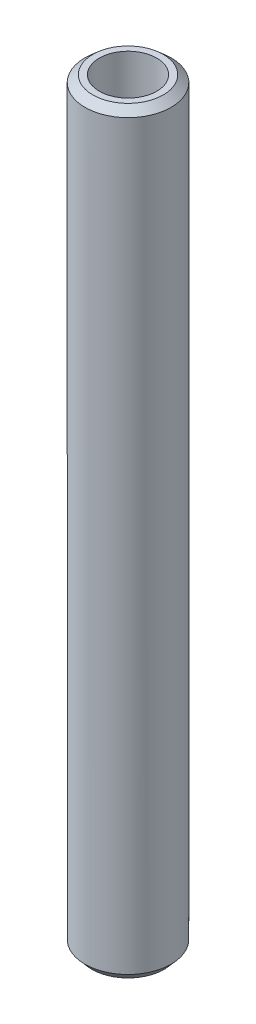
SolidWorks part; units mm, degrees
ref_plane "Front Plane" through (0, 0, 0) normal (0, 0, 1) x (1, 0, 0)
ref_plane "Top Plane" through (0, 0, 0) normal (0, 1, 0) x (1, 0, 0)
ref_plane "Right Plane" through (0, 0, 0) normal (1, 0, 0) x (0, 0, -1)
sketch "Sketch1" plane through (0, 0, 0) normal (0, 1, 0) x (1, 0, 0)
  circle A0 centre (0, 0) radius 10
  dimension "SHAFT_OD" = 20
extrude "Boss-Extrude1" add sketch "Sketch1" along normal blind 175.934
sketch "Sketch2" plane through (0, 0, 0) normal (0, 1, 0) x (1, 0, 0)
  circle A0 centre (0, 0) radius 6.6821
  dimension "BORE_D" = 13.3642
extrude "Cut-Extrude1" cut sketch "Sketch2" along normal through all
chamfer "Chamfer1" distance 1.5896 angle 48.945 2 edges at (0, 175.934, 10) (0, 0, 10) first distance on face at (0, 175.934, 10) first distance on face at (0, 0, 6.6821)
